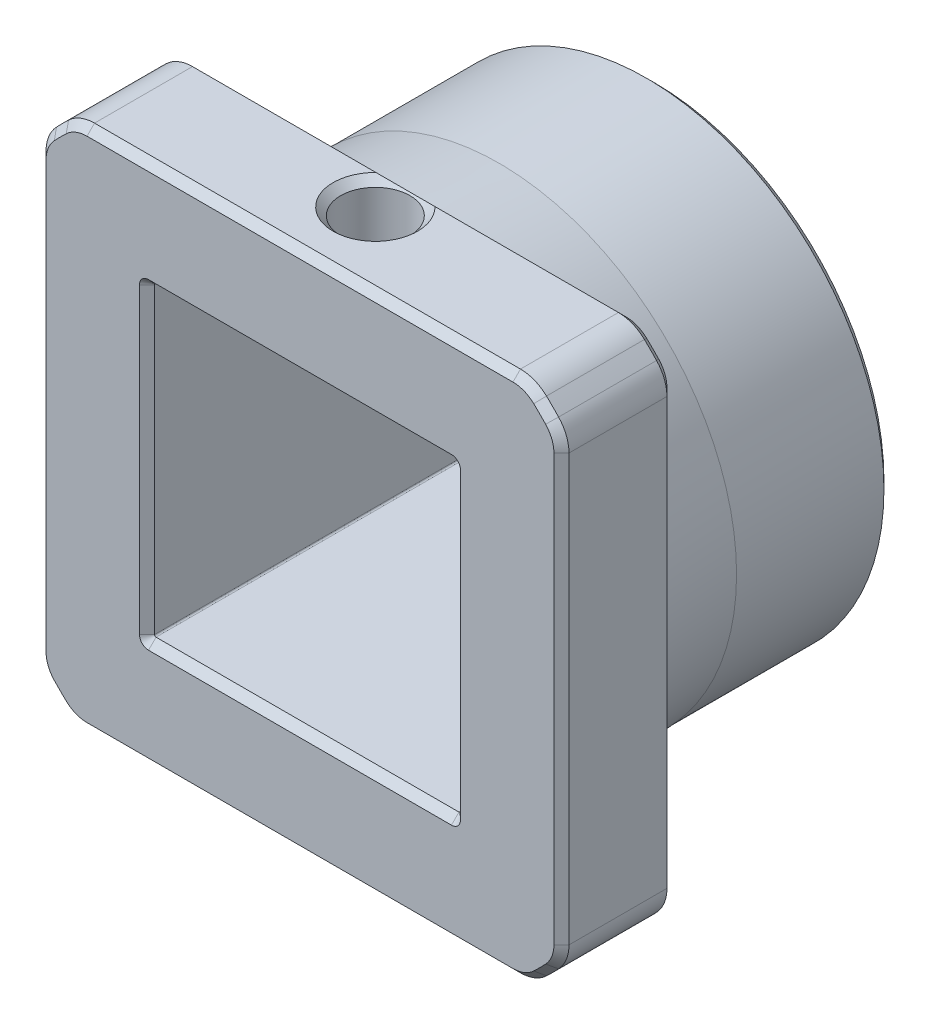
SolidWorks part; units mm, degrees
ref_plane "Front" through (0, 0, 0) normal (0, 0, 1) x (1, 0, 0)
ref_plane "Top" through (0, 0, 0) normal (0, 1, 0) x (1, 0, 0)
ref_plane "Right" through (0, 0, 0) normal (1, 0, 0) x (0, 0, -1)
sketch "Skizze1" plane through (0, 0, 0) normal (0, 0, 1) x (1, 0, 0)
  line L1 (-10.15, -10.15) -> (10.15, -10.15)
  line L2 (-10.15, -10.15) -> (-10.15, 10.15)
  line L3 (-10.15, 10.15) -> (10.15, 10.15)
  line L4 (10.15, -10.15) -> (10.15, 10.15)
  line L5 (-10.15, -10.15) -> (10.15, 10.15) construction
  line L6 (-10.15, 10.15) -> (10.15, -10.15) construction
  circle A0 centre (0, 0) radius 15.75
  point P0 (0, 0)
  dimension "D2" = 31.5
  dimension "D1" = 20.3
extrude "Aufsatz-Linear austragen1" add sketch "Skizze1" along normal blind 16
sketch "Skizze2" plane through (0, 0, 16) normal (0, 0, 1) x (1, 0, 0)
  line L0 (-15.0989, 17.35) -> (15.0989, 17.35)
  line L1 (-10.15, -10.15) -> (10.15, -10.15)
  line L2 (-10.15, -10.15) -> (-10.15, 10.15)
  line L3 (-10.15, 10.15) -> (10.15, 10.15)
  line L4 (10.15, -10.15) -> (10.15, 10.15)
  line L5 (-10.15, -10.15) -> (10.15, 10.15) construction
  line L6 (-10.15, 10.15) -> (10.15, -10.15) construction
  line L7 (0, 0) -> (13.8508, 0) construction
  line L8 (0, 0) -> (0, 13.2524) construction
  line L9 (17.35, -15.0989) -> (17.35, 15.0989)
  line L10 (15.0989, -17.35) -> (-15.0989, -17.35)
  line L11 (-17.35, 15.0989) -> (-17.35, -15.0989)
  arc A0 (-15.0989, 17.35) -> (-17.35, 15.0989) centre (0, 0) ccw
  arc A2 (-17.35, -15.0989) -> (-15.0989, -17.35) centre (0, 0) ccw
  arc A3 (15.0989, -17.35) -> (17.35, -15.0989) centre (0, 0) ccw
  arc A4 (17.35, 15.0989) -> (15.0989, 17.35) centre (0, 0) ccw
  dimension "D1" = 46
  dimension "D2" = 7.2
extrude "Aufsatz-Linear austragen2" add sketch "Skizze2" along normal blind 7.5
sketch "Skizze3" plane through (0, 17.35, 0) normal (0, 1, 0) x (1, 0, 0)
  line L0 (0, -13.5) -> (0, -23.5) construction
  line L2 (15.0989, -23.5) -> (-15.0989, -23.5) construction
  circle A0 centre (0, -18.5) radius 2.3
  dimension "D1" = 4.6
  dimension "D2" = 10
extrude "Schnitt-Linear austragen1" cut sketch "Skizze3" against normal up to next
pattern_circular "Kreismuster1" [suppressed] count 2 over 90 reverse direction yes of bodies 103
chamfer "Chamfer1" distance 0.4 angle 86 1 edges at (15.75, 0, 16) first distance on face at (15.75, 0, 16)
fillet "Verrundung1" radius 0.1 4 edges at (10.15, -10.15, 11.75) (-10.15, -10.15, 11.75) (-10.15, 10.15, 11.75) (10.15, 10.15, 11.75)
fillet "Verrundung2" radius 2.5 8 edges at (-17.35, -15.0989, 19.75) (-15.0989, -17.35, 19.75) (15.0989, -17.35, 19.75) (17.35, -15.0989, 19.75) (17.35, 15.0989, 19.75) (15.0989, 17.35, 19.75) (-17.35, 15.0989, 19.75) (-15.0989, 17.35, 19.75)
chamfer "Fase1" distance 0.5 angle 45 35 edges at (-10.1207, -10.1207, 0) (-10.15, 0, 0) (-10.1207, 10.1207, 0) (0, 10.15, 0) (10.1207, 10.1207, 0) (10.15, 0, 0) (10.1207, -10.1207, 0) (0, -10.15, 0) (15.75, 0, 0) (-10.1207, 10.1207, 23.5) (-10.15, 0, 23.5) (-10.1207, -10.1207, 23.5) (0, -10.15, 23.5) (10.1207, -10.1207, 23.5) (10.15, 0, 23.5) (10.1207, 10.1207, 23.5) (0, 10.15, 23.5) (-17.1714, 15.0605, 23.5) (-16.2635, 16.2635, 23.5) (-15.0605, 17.1714, 23.5) (0, 17.35, 23.5) (15.0605, 17.1714, 23.5) (16.2635, 16.2635, 23.5) (17.1714, 15.0605, 23.5) (17.35, 0, 23.5) (17.1714, -15.0605, 23.5) (16.2635, -16.2635, 23.5) (15.0605, -17.1714, 23.5) (0, -17.35, 23.5) (-15.0605, -17.1714, 23.5) (-16.2635, -16.2635, 23.5) (-17.1714, -15.0605, 23.5) (-17.35, 0, 23.5) (0, 10.15, 16.2) (0, 17.35, 20.8)
chamfer "Fase2" [suppressed] distance 0.3 angle 45
chamfer "Fase3" [suppressed] distance 0.5 angle 45
chamfer "Fase4" distance 0.5 angle 45 17 edges at (0, -17.35, 16) (15.0605, -17.1714, 16) (-15.0605, -17.1714, 16) (16.2635, -16.2635, 16) (-16.2635, -16.2635, 16) (17.1714, -15.0605, 16) (-17.1714, -15.0605, 16) (17.35, 0, 16) (-17.35, 0, 16) (17.1714, 15.0605, 16) (-17.1714, 15.0605, 16) (16.2635, 16.2635, 16) (-16.2635, 16.2635, 16) (15.0605, 17.1714, 16) (-15.0605, 17.1714, 16) (7.6967, 17.35, 16) (-7.6967, 17.35, 16)
